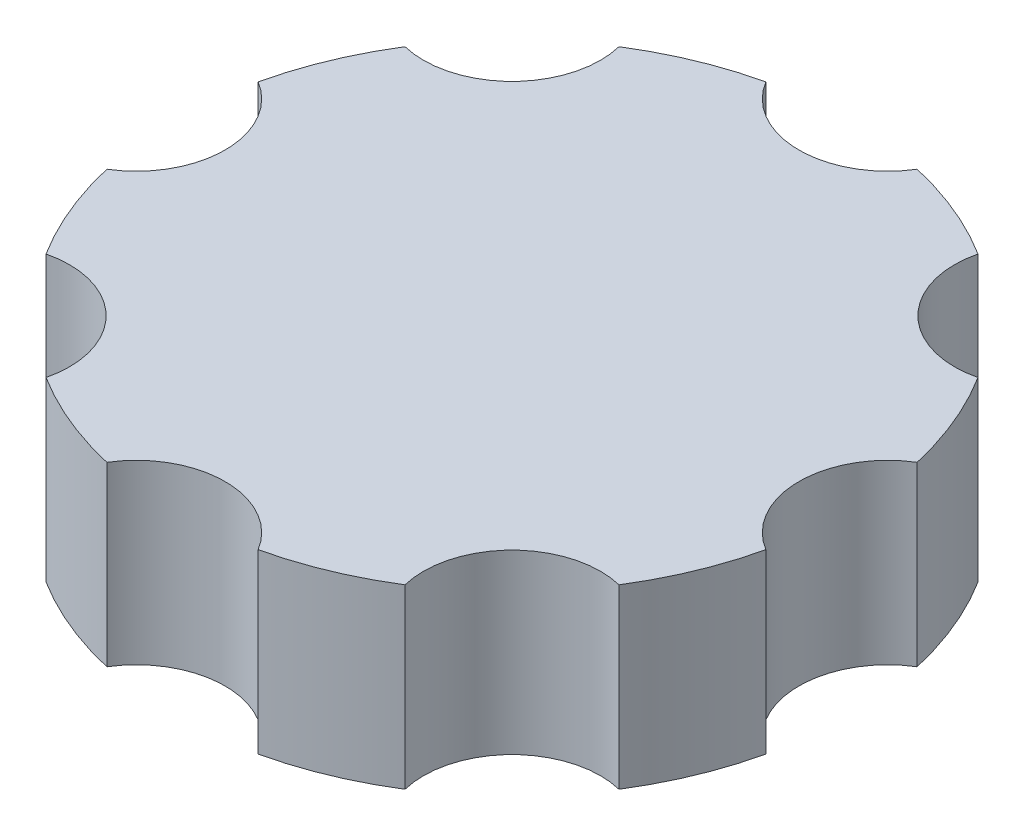
SolidWorks part; units mm, degrees
ref_plane "Front Plane" through (0, 0, 0) normal (0, 0, 1) x (1, 0, 0)
ref_plane "Top Plane" through (0, 0, 0) normal (0, 1, 0) x (1, 0, 0)
ref_plane "Right Plane" through (0, 0, 0) normal (1, 0, 0) x (0, 0, -1)
sketch "Sketch1" plane through (0, 0, 0) normal (0, 1, 0) x (1, 0, 0)
  line L0 (0, -21.2055) -> (21.2055, -21.2055) construction
  line L1 (0, -21.2055) -> (14.9946, -14.9946) construction
  line L2 (14.9946, -14.9946) -> (21.2055, 0) construction
  line L3 (21.2055, 0) -> (14.9946, 14.9946) construction
  line L4 (14.9946, 14.9946) -> (0, 21.2055) construction
  line L5 (0, 21.2055) -> (-14.9946, 14.9946) construction
  line L6 (-14.9946, 14.9946) -> (-21.2055, 0) construction
  line L7 (-21.2055, 0) -> (-14.9946, -14.9946) construction
  line L8 (-14.9946, -14.9946) -> (0, -21.2055) construction
  line L9 (21.2055, -21.2055) -> (21.2055, 0) construction
  arc A1 (4.2719, -18.6073) -> (-4.2719, -18.6073) centre (0, -21.2055) ccw
  arc A2 (-10.1366, -16.178) -> (-16.178, -10.1366) centre (-14.9946, -14.9946) ccw
  arc A3 (-18.6073, -4.2719) -> (-18.6073, 4.2719) centre (-21.2055, 0) ccw
  arc A4 (-16.178, 10.1366) -> (-10.1366, 16.178) centre (-14.9946, 14.9946) ccw
  arc A5 (-4.2719, 18.6073) -> (4.2719, 18.6073) centre (0, 21.2055) ccw
  arc A6 (10.1366, 16.178) -> (16.178, 10.1366) centre (14.9946, 14.9946) ccw
  arc A7 (-10.1366, -16.178) -> (-4.2719, -18.6073) centre (0, 0) ccw
  arc A8 (-16.178, -10.1366) -> (-18.6073, -4.2719) centre (0, 0) cw
  arc A9 (-18.6073, 4.2719) -> (-16.178, 10.1366) centre (0, 0) cw
  arc A10 (-10.1366, 16.178) -> (-4.2719, 18.6073) centre (0, 0) cw
  arc A11 (4.2719, 18.6073) -> (10.1366, 16.178) centre (0, 0) cw
  arc A13 (18.6073, 4.2719) -> (18.6073, -4.2719) centre (21.2055, 0) ccw
  arc A14 (16.178, -10.1366) -> (10.1366, -16.178) centre (14.9946, -14.9946) ccw
  arc A15 (4.2719, -18.6073) -> (10.1366, -16.178) centre (0, 0) ccw
  arc A16 (16.178, -10.1366) -> (18.6073, -4.2719) centre (0, 0) ccw
  arc A17 (18.6073, 4.2719) -> (16.178, 10.1366) centre (0, 0) ccw
  circle A18 centre (0, 0) radius 19.5913 construction
  point P23 (0, 0)
  point P26 (21.1823, -21.1823)
  point P27 (-4.2719, -18.6073)
  point P29 (-4.2719, -18.6073)
  point P31 (-7.3059, -17.6381)
  point P33 (-7.4973, -18.1)
  point P37 (-10.1366, -16.178)
  dimension "D1" = 16.23
  dimension "D2" = 0.5
  dimension "D3" = 5
  dimension "D4" = 8
extrude "Boss-Extrude1" add sketch "Sketch1" along normal blind 10
